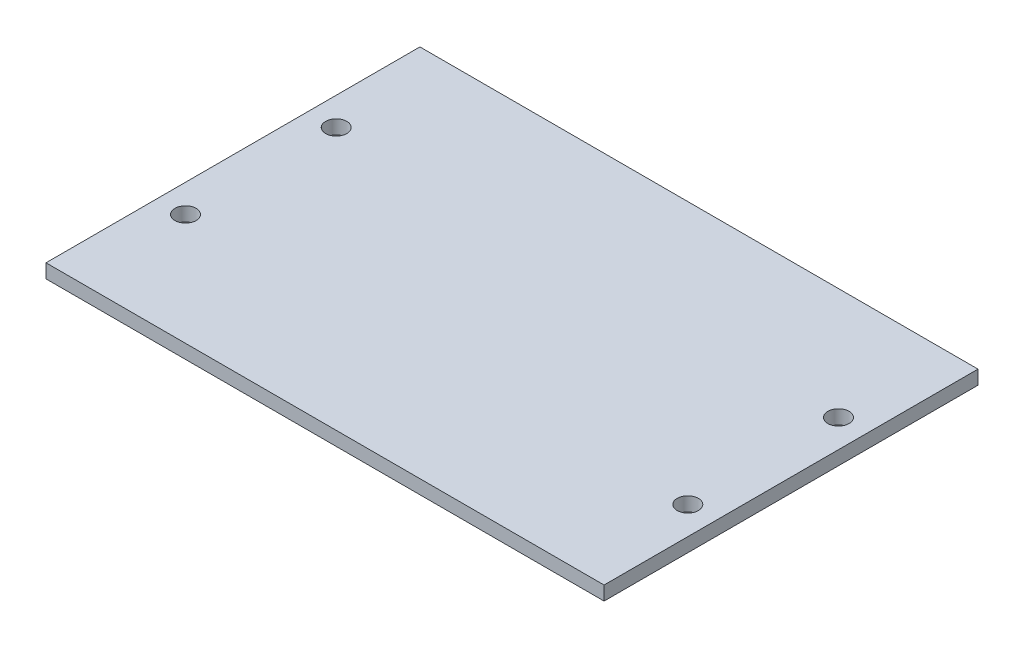
SolidWorks part; units mm, degrees
material "AISI Type A2 Tool Steel"
ref_plane "Front Plane" through (0, 0, 0) normal (0, 0, 1) x (1, 0, 0)
ref_plane "Top Plane" through (0, 0, 0) normal (0, 1, 0) x (1, 0, 0)
ref_plane "Right Plane" through (0, 0, 0) normal (1, 0, 0) x (0, 0, -1)
sketch "Sketch1" plane through (0, 0, 0) normal (0, 1, 0) x (1, 0, 0)
  line L1 (-38.8384, 47.6545) -> (88.1616, 47.6545)
  line L2 (-38.8384, 47.6545) -> (-38.8384, -37.4355)
  line L3 (-38.8384, -37.4355) -> (88.1616, -37.4355)
  line L4 (88.1616, 47.6545) -> (88.1616, -37.4355)
  dimension "D1" = 127
  dimension "D2" = 85.09
extrude "Boss-Extrude1" add sketch "Sketch1" along normal blind 3.175
sketch "Sketch2" plane through (0, 3.175, 0) normal (0, 1, 0) x (1, 0, 0)
  line L0 (88.1616, -37.4355) -> (88.1616, 47.6545) construction
  line L1 (-38.8384, -37.4355) -> (88.1616, -37.4355) construction
  line L3 (88.1616, 47.6545) -> (-38.8384, 47.6545) construction
  line L4 (-38.8384, 47.6545) -> (-38.8384, -37.4355) construction
  circle A0 centre (81.8116, -12.0355) radius 2.413
  circle A1 centre (81.8116, 22.2545) radius 2.413
  circle A2 centre (-32.4884, 22.2545) radius 2.413
  circle A3 centre (-32.4884, -12.0355) radius 2.413
  point P0 (81.8116, -12.0355)
  point P1 (-32.4884, -12.0355)
  point P2 (81.8116, 22.2545)
  point P9 (-32.4884, 22.2545)
  dimension "D5" = 4.826
  dimension "D1" = 6.35
  dimension "D2" = 6.35
  dimension "D3" = 25.4
  dimension "D4" = 25.4
extrude "Cut-Extrude1" cut sketch "Sketch2" against normal through all
